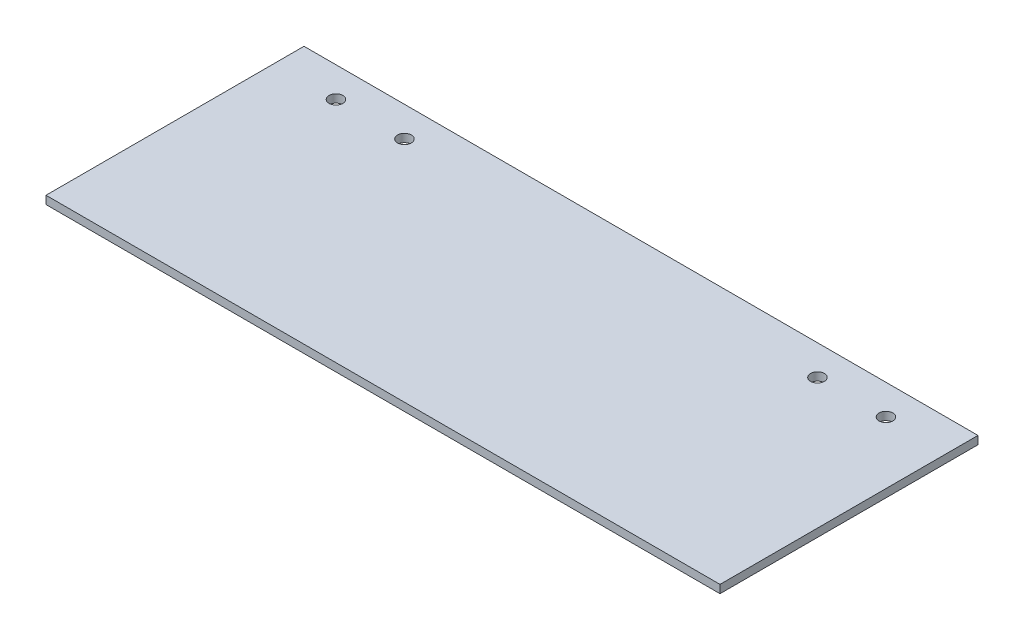
SolidWorks part; units mm, degrees
ref_plane "Front Plane" through (0, 0, 0) normal (0, 0, 1) x (1, 0, 0)
ref_plane "Top Plane" through (0, 0, 0) normal (0, 1, 0) x (1, 0, 0)
ref_plane "Right Plane" through (0, 0, 0) normal (1, 0, 0) x (0, 0, -1)
sketch "Sketch1" plane through (0, 0, 0) normal (0, 1, 0) x (1, 0, 0)
  line L0 (125, 95.7) -> (125, 0) construction
  line L1 (0, 95.7) -> (250, 95.7)
  line L2 (0, 95.7) -> (0, 0)
  line L3 (0, 0) -> (250, 0)
  line L4 (250, 95.7) -> (250, 0)
  circle A0 centre (23, 84.56) radius 2.564
  circle A1 centre (48.4, 84.56) radius 2.564
  circle A2 centre (201.6, 84.56) radius 2.564
  circle A3 centre (227, 84.56) radius 2.564
  dimension "D2" = 5.128
  dimension "D1" = 250
  dimension "D3" = 25.4
  dimension "D4" = 23
  dimension "D5" = 11.14
  dimension "D6" = 84.56
extrude "Boss-Extrude1" add sketch "Sketch1" along normal blind 3
equation "\"cf_tube_outer_diameter\"= 25mm"
equation "\"cf_tube_inner_diameter\" = 21mm"
equation "\"mid_plate_mid_to_top\" = 100mm"
equation "\"mid_plate_mid_to_bottom\" = 30mm"
equation "\"mid_plate_horizontal_spacing\"=250mm"
equation "\"cf_plate_thickness\" =3mm"
equation "\"mid_tube_length\" = 500mm"
equation "\"mid_plate_bottom_width\" = 180mm"
equation "\"mid_support_plate_distance\" = 250mm"
equation "\"nut_strip_2_hole_distance\" = 7mm"
equation "\"nut_strip_hole_diameter\" = 2.5mm"
equation "\"nut_strip_hole_to_edge_distance\"= 2.5mm"
